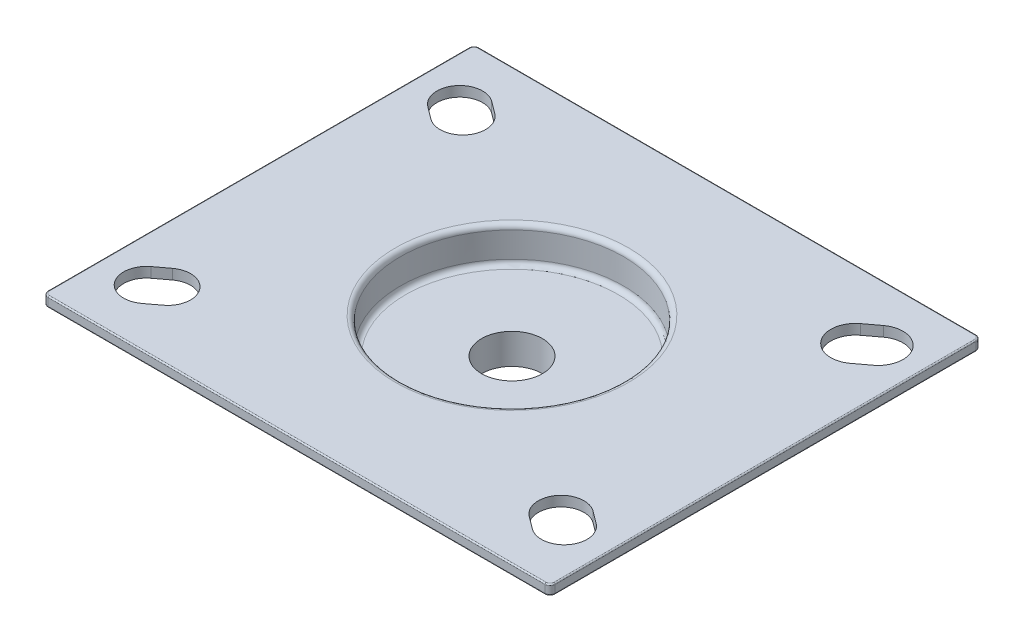
SolidWorks part; units mm, degrees
material "AISI 304"
ref_plane "Спереди" through (0, 0, 0) normal (0, 0, 1) x (1, 0, 0)
ref_plane "Сверху" through (0, 0, 0) normal (0, 1, 0) x (1, 0, 0)
ref_plane "Справа" through (0, 0, 0) normal (1, 0, 0) x (0, 0, -1)
sketch "Эскиз2" plane through (0, 0, 0) normal (0, 1, 0) x (1, 0, 0)
  line L0 (38.7085, 29.0314) -> (41.2915, 30.9686) construction
  line L1 (-50, -42.5) -> (50, -42.5)
  line L2 (-50, -42.5) -> (-50, 42.5)
  line L3 (-50, 42.5) -> (50, 42.5)
  line L4 (50, -42.5) -> (50, 42.5)
  line L5 (-50, -42.5) -> (50, 42.5) construction
  line L6 (-50, 42.5) -> (50, -42.5) construction
  line L7 (-40, -30) -> (40, -30) construction
  line L8 (-40, -30) -> (-40, 30) construction
  line L9 (-40, 30) -> (40, 30) construction
  line L10 (40, -30) -> (40, 30) construction
  line L11 (-40, -30) -> (40, 30) construction
  line L12 (-40, 30) -> (40, -30) construction
  line L13 (-50, 0) -> (50, 0) construction
  line L14 (35.7977, 32.9124) -> (38.3808, 34.8496)
  line L15 (41.6192, 25.1504) -> (44.2023, 27.0876)
  line L16 (0, 42.5) -> (0, -42.5) construction
  line L17 (-41.2, 30.9) -> (-38.8, 29.1) construction
  line L18 (-41.2, -30.9) -> (-38.8, -29.1) construction
  line L19 (-38.5, 34.5) -> (-36.1, 32.7)
  line L20 (-43.9, 27.3) -> (-41.5, 25.5)
  line L21 (38.5, -34.5) -> (36.1, -32.7)
  line L22 (-43.9, -27.3) -> (-41.5, -25.5)
  line L23 (-38.5, -34.5) -> (-36.1, -32.7)
  line L24 (41.2, -30.9) -> (38.8, -29.1) construction
  line L25 (43.9, -27.3) -> (41.5, -25.5)
  arc A0 (35.7977, 32.9124) -> (41.6192, 25.1504) centre (38.7085, 29.0314) ccw
  arc A1 (44.2023, 27.0876) -> (38.3808, 34.8496) centre (41.2915, 30.9686) ccw
  arc A2 (-38.5, 34.5) -> (-43.9, 27.3) centre (-41.2, 30.9) ccw
  arc A3 (-41.5, 25.5) -> (-36.1, 32.7) centre (-38.8, 29.1) ccw
  arc A4 (-43.9, -27.3) -> (-38.5, -34.5) centre (-41.2, -30.9) ccw
  arc A5 (-36.1, -32.7) -> (-41.5, -25.5) centre (-38.8, -29.1) ccw
  arc A6 (38.5, -34.5) -> (43.9, -27.3) centre (41.2, -30.9) ccw
  arc A7 (41.5, -25.5) -> (36.1, -32.7) centre (38.8, -29.1) ccw
  circle A8 centre (0, 0) radius 6
  point P0 (0, 0)
  point P5 (0, 0)
  point P15 (40, 30)
  point P26 (-40, 30)
  point P32 (40, -30)
  point P33 (-40, -30)
  dimension "D1" = 80
  dimension "D2" = 60
  dimension "D3" = 100
  dimension "D4" = 85
extrude "Бобышка-Вытянуть1" add sketch "Эскиз2" along normal blind 2
sketch "Эскиз3" plane through (0, 2, 0) normal (0, 1, 0) x (1, 0, 0)
  circle A0 centre (0, 0) radius 25
extrude "Бобышка-Вытянуть2" add sketch "Эскиз3" against normal blind 10
shell "Оболочка1" thickness 3 removed face at (-40, 2, 30)
fillet "Скругление1" radius 1 4 edges at (0, 0, -25) (0, -8, 25) (0, -5, 22) (0, 2, -22)
sketch "Эскиз4" plane through (0, -5, 0) normal (0, 1, 0) x (1, 0, 0)
  circle A0 centre (0, 0) radius 6
sketch "Эскиз5" plane through (0, -5, 0) normal (0, 1, 0) x (1, 0, 0)
  circle A0 centre (0, 0) radius 13.3323
extrude "Бобышка-Вытянуть3" add sketch "Эскиз5" against normal blind 6
extrude "Вырез-Вытянуть2" cut sketch "Эскиз4" against normal mid plane 39.8 contours A0
fillet "Скругление3" radius 1 4 edges at (50, 1, 42.5) (50, 1, -42.5) (-50, 1, -42.5) (-50, 1, 42.5)
fillet "Скругление4" radius 0.25 16 edges at (-49.7071, 0, 42.2071) (-50, 0, 0) (-49.7071, 0, -42.2071) (0, 0, -42.5) (49.7071, 0, -42.2071) (50, 0, 0) (49.7071, 0, 42.2071) (-49.7071, 2, 42.2071) (-50, 2, 0) (-49.7071, 2, -42.2071) (0, 2, -42.5) (49.7071, 2, -42.2071) (50, 2, 0) (49.7071, 2, 42.2071) (0, 0, 42.5) (0, 2, 42.5)
